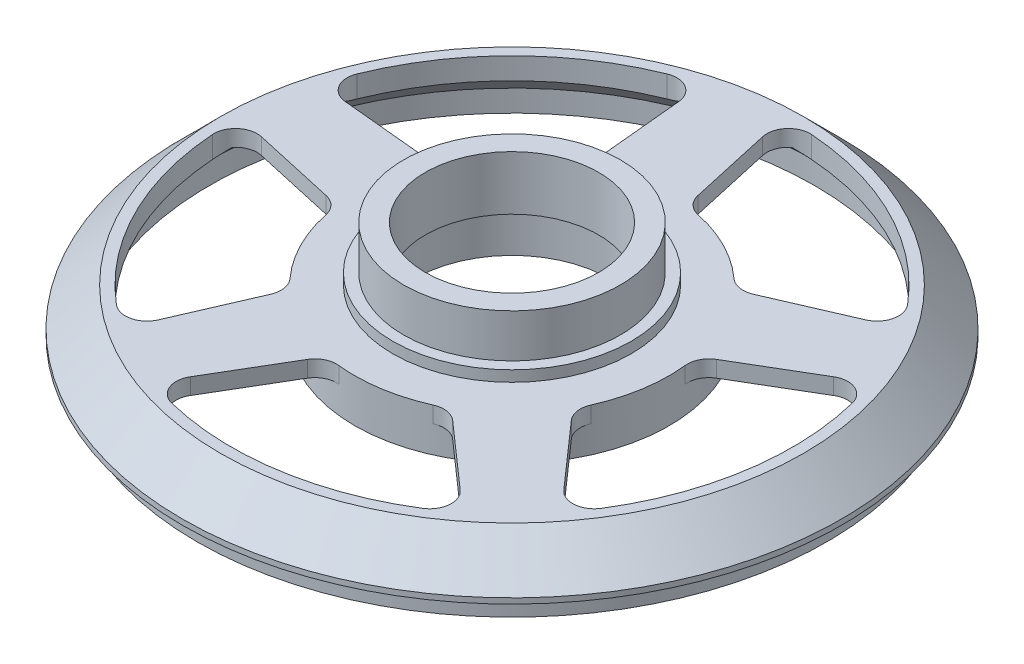
SolidWorks part; units mm, degrees
note: '?' marks a value the reader was unsure of.
ref_plane "Front Plane" through (0, 0, 0) normal (0, 0, 1) x (1, 0, 0)
ref_plane "Top Plane" through (0, 0, 0) normal (0, 1, 0) x (1, 0, 0)
ref_plane "Right Plane" through (0, 0, 0) normal (1, 0, 0) x (0, 0, -1)
ref_axis "Axis1" through (0, 0, 0) along (0, 1, 0)?
sketch "Sketch1" plane through (0, 0, 0) normal (0, 0, 1) x (1, 0, 0)
  line L0 (-30.4, 6) -> (-30.4, 6.5)
  line L2 (-30.4, 6.5) -> (-26.9, 10)
  line L4 (-30.4, 6) -> (-29.05, 6)
  line L5 (30.4, 6) -> (-30.4, 6) construction
  line L6 (-29.05, 6) -> (-29.05, 4)
  line L7 (-29.05, 4) -> (-27.9, 4)
  line L8 (-24.8973, 4) -> (-28.5481, 4) construction
  line L9 (-27.9, 4) -> (-27.9, 6)
  line L12 (-14.5, 6) -> (-9, 6)
  line L13 (-9, 6) -> (-9, 10)
  line L14 (-8.8, 6) -> (8.8, 6) construction
  line L15 (-9, 10) -> (-8, 10)
  line L16 (-8, 10) -> (-8, 15)
  line L18 (-27.9, 6) -> (-25.4, 8.5)
  line L19 (-8, 15) -> (-10, 15)
  line L20 (-10, 15) -> (-10, 11)
  line L21 (-10, 11) -> (-11, 11)
  line L22 (-11, 11) -> (-11, 10)
  line L23 (-11, 10) -> (-26.9, 10)
  line L24 (-29.1, 6) -> (-29.1, -4) construction
  line L25 (0, 0) -> (0, -50000) construction
  line L26 (-7, 10) -> (7, 10) construction
  line L27 (-25.4, 8.5) -> (-14.5, 8.5)
  line L28 (-14.5, 8.5) -> (-14.5, 6)
  line L29 (22.7479, 7) -> (-22.7479, 7) construction
  dimension "D2" = 0.05
  dimension "D3" = 2.5
  dimension "D4" = 1.5
  dimension "D5" = 1.5
  dimension "D6" = 135
  dimension "D7" = 1
  dimension "D8" = 1
  dimension "D9" = 20
  dimension "D10" = 4
  dimension "D11" = 1
  dimension "D12" = 5.5
  dimension "D13" = 0.5
  dimension "D14" = 18
revolve "Revolve1" add sketch "Sketch1" angle 360 about L25
sketch "Sketch2" plane through (0, 0, 0) normal (0, 1, 0) x (1, 0, 0)
  line L0 (0, 0) -> (-18.3141, 18.3141) construction
  line L1 (2.3195, 0) -> (50002.3195, 0) construction
  line L2 (-7.2011, 24.8788) -> (-6.0887, 13.1597)
  line L3 (-24.8788, 7.2011) -> (-13.1597, 6.0887)
  arc A0 (-7.2011, 24.8788) -> (-24.8788, 7.2011) centre (0, 0) ccw
  arc A1 (-6.0887, 13.1597) -> (-13.1597, 6.0887) centre (0, 0) ccw
  circle A3 centre (0, 0) radius 14.5 construction
  circle A4 centre (0, 0) radius 27.9 construction
  point P1 (-10.253, 10.253)
  dimension "D3" = 2
  dimension "D1" = 45
  dimension "D2" = 10
  dimension "D4" = 25
extrude "Cut-Extrude1" cut sketch "Sketch2" along normal through all
fillet "Fillet1" radius 2 4 edges at (-7.2011, 9, -24.8788) (-24.8788, 9, -7.2011) (-6.0887, 9.25, -13.1597) (-13.1597, 9.25, -6.0887)
pattern_circular "CirPattern1" count 5 over 360 about axis through (0, 0, 0) along (0, 1, 0) of "Cut-Extrude1", "Fillet1"
sketch "Sketch3" plane through (0, 0, 0) normal (0, 0, 1) x (1, 0, 0)
  line L0 (0, 0) -> (0, -50000) construction
  line L1 (-10, 9) -> (-14, 9) construction
  line L2 (-14, 0.6749) -> (-10, 0.6749)
  line L3 (-14, 0.6749) -> (-14, 9)
  line L4 (-14, 9) -> (-10, 9)
  line L5 (-10, 0.6749) -> (-10, 9)
  point P7 (-12, 9)
  dimension "D1" = 4
  dimension "D2" = 12
revolve "Cut-Revolve1" [suppressed] cut sketch "Sketch3" angle 360 about L0
sketch "Sketch4" plane through (0, 0, 0) normal (0, 1, 0) x (1, 0, 0)
  circle A0 centre (12, 0) radius 2.1
  dimension "D1" = 4.2
  dimension "D2" = 12
extrude "Cut-Extrude2" cut sketch "Sketch4" against normal through all from surface at 9
pattern_circular "CirPattern2" count 14 over 360 about axis through (0, 0, 0) along (0, 1, 0) of "Cut-Extrude2"
